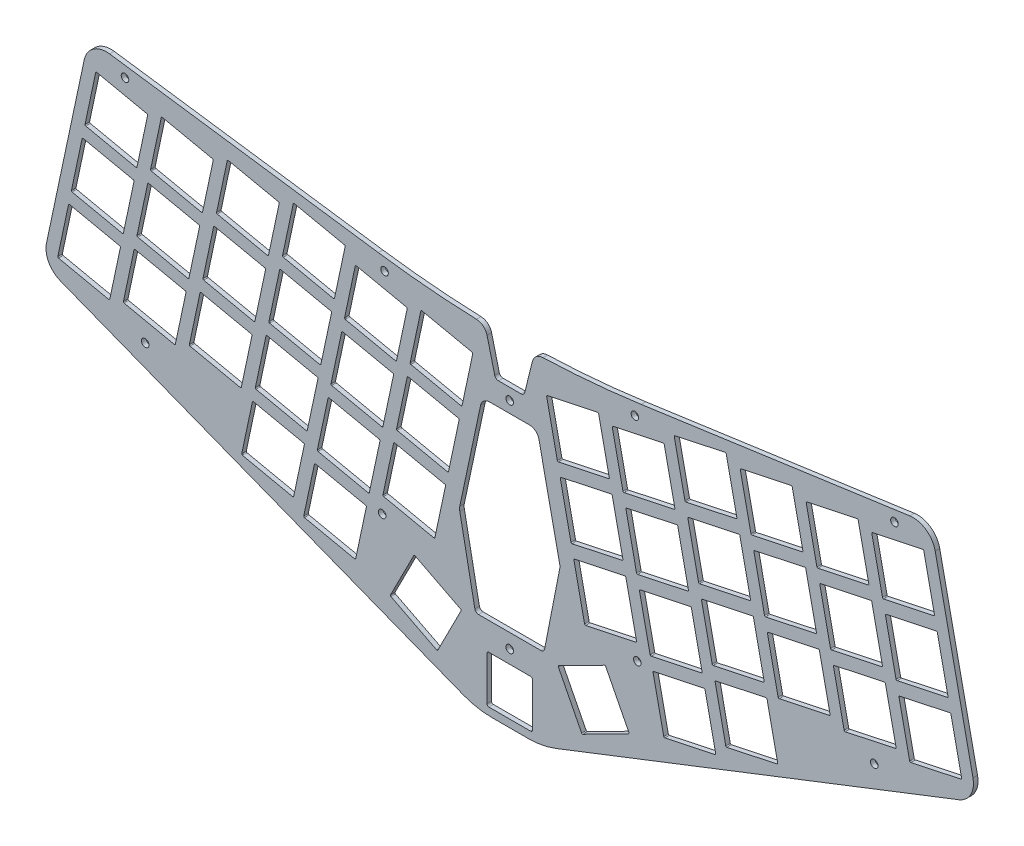
SolidWorks part; units mm, degrees
ref_plane "Front Plane" through (0, 0, 0) normal (0, 0, 1) x (1, 0, 0)
ref_plane "Top Plane" through (0, 0, 0) normal (0, 1, 0) x (1, 0, 0)
ref_plane "Right Plane" through (0, 0, 0) normal (1, 0, 0) x (0, 0, -1)
sketch "Model" plane through (0, 0, 0) normal (0, 0, 1) x (1, 0, 0)
  line L0 (118.9761, -36.3417) -> (119.3386, -36.3417)
  line L1 (109.9761, -36.3417) -> (109.6135, -36.3417)
  line L2 (130.2178, -33.5671) -> (126.6009, -34.9766)
  line L3 (98.7344, -33.5671) -> (102.3512, -34.9766)
  line L4 (114.4761, -36.3417) -> (109.9761, -36.3417)
  line L5 (114.4761, -36.3417) -> (118.9761, -36.3417)
  line L6 (118.4251, 42.1791) -> (120.4508, 50.3035)
  line L7 (110.527, 42.1791) -> (108.5014, 50.3035)
  line L8 (130.2178, -33.5671) -> (232.9153, 6.4558)
  line L9 (236.6055, 13.2938) -> (226.6558, 60.1035)
  line L10 (219.9519, 64.7976) -> (149.1302, 54.8443)
  line L11 (79.822, 54.8443) -> (9.0003, 64.7976)
  line L12 (2.2964, 60.1035) -> (-7.6533, 13.2938)
  line L13 (-3.9631, 6.4558) -> (98.7344, -33.5671)
  line L14 (111.4973, 41.421) -> (117.4548, 41.421)
  line L15 (119.9761, -34.3417) -> (108.9761, -34.3417)
  line L16 (120.4761, -22.3417) -> (120.4761, -33.8417)
  line L17 (108.9761, -21.8417) -> (119.9761, -21.8417)
  line L18 (108.4761, -33.8417) -> (108.4761, -22.3417)
  line L19 (123.6714, -13.7578) -> (127.6435, 6.5155)
  line L20 (105.2808, -13.7578) -> (101.3087, 6.5155)
  line L21 (106.2621, -14.5655) -> (122.69, -14.5655)
  line L22 (109.4761, 35.421) -> (109.2316, 35.421)
  line L23 (119.4761, 35.421) -> (119.7205, 35.421)
  line L24 (109.4761, 35.421) -> (119.4761, 35.421)
  line L25 (127.6339, 7.716) -> (122.1659, 33.4408)
  line L26 (101.3183, 7.716) -> (106.7863, 33.4408)
  line L27 (230.5128, 25.1235) -> (217.3078, 22.3167)
  line L28 (217.1153, 22.0202) -> (219.9221, 8.8152)
  line L29 (220.2186, 8.6226) -> (233.4236, 11.4294)
  line L30 (233.6161, 11.7259) -> (230.8093, 24.9309)
  line L31 (226.9263, 41.9965) -> (213.7213, 39.1897)
  line L32 (213.5288, 38.8932) -> (216.3356, 25.6882)
  line L33 (216.6321, 25.4957) -> (229.8371, 28.3025)
  line L34 (230.0297, 28.599) -> (227.2228, 41.804)
  line L35 (223.3399, 58.8696) -> (210.1349, 56.0628)
  line L36 (209.9423, 55.7663) -> (212.7491, 42.5613)
  line L37 (213.0456, 42.3687) -> (226.2506, 45.1755)
  line L38 (226.4432, 45.472) -> (223.6364, 58.677)
  line L39 (213.2239, 23.4933) -> (200.0189, 20.6865)
  line L40 (199.8264, 20.39) -> (202.6332, 7.185)
  line L41 (202.9297, 6.9924) -> (216.1347, 9.7992)
  line L42 (216.3273, 10.0958) -> (213.5205, 23.3007)
  line L43 (209.6375, 40.3663) -> (196.4325, 37.5595)
  line L44 (196.2399, 37.263) -> (199.0467, 24.058)
  line L45 (199.3432, 23.8655) -> (212.5482, 26.6723)
  line L46 (212.7408, 26.9688) -> (209.934, 40.1738)
  line L47 (206.051, 57.2394) -> (192.846, 54.4326)
  line L48 (192.6534, 54.1361) -> (195.4602, 40.9311)
  line L49 (195.7568, 40.7385) -> (208.9618, 43.5453)
  line L50 (209.1543, 43.8418) -> (206.3475, 57.0468)
  line L51 (195.8311, 22.3522) -> (182.6261, 19.5454)
  line L52 (182.4336, 19.2489) -> (185.2404, 6.0439)
  line L53 (185.5369, 5.8513) -> (198.7419, 8.6581)
  line L54 (198.9344, 8.9546) -> (196.1276, 22.1596)
  line L55 (192.2446, 39.2252) -> (179.0396, 36.4184)
  line L56 (178.8471, 36.1219) -> (181.6539, 22.9169)
  line L57 (181.9504, 22.7244) -> (195.1554, 25.5312)
  line L58 (195.348, 25.8277) -> (192.5412, 39.0327)
  line L59 (188.6582, 56.0983) -> (175.4532, 53.2915)
  line L60 (175.2606, 52.995) -> (178.0674, 39.79)
  line L61 (178.3639, 39.5974) -> (191.5689, 42.4042)
  line L62 (191.7615, 42.7007) -> (188.9547, 55.9057)
  line L63 (182.0248, 4.338) -> (168.8198, 1.5312)
  line L64 (168.6272, 1.2347) -> (171.434, -11.9703)
  line L65 (171.7305, -12.1628) -> (184.9355, -9.356)
  line L66 (185.1281, -9.0595) -> (182.3213, 4.1455)
  line L67 (178.4383, 21.2111) -> (165.2333, 18.4043)
  line L68 (165.0407, 18.1078) -> (167.8475, 4.9028)
  line L69 (168.1441, 4.7102) -> (181.3491, 7.517)
  line L70 (181.5416, 7.8135) -> (178.7348, 21.0185)
  line L71 (174.8518, 38.0841) -> (161.6468, 35.2773)
  line L72 (161.4543, 34.9808) -> (164.2611, 21.7758)
  line L73 (164.5576, 21.5833) -> (177.7626, 24.3901)
  line L74 (177.9551, 24.6866) -> (175.1483, 37.8916)
  line L75 (171.2653, 54.9572) -> (158.0603, 52.1504)
  line L76 (157.8678, 51.8539) -> (160.6746, 38.6489)
  line L77 (160.9711, 38.4563) -> (174.1761, 41.2631)
  line L78 (174.3687, 41.5596) -> (171.5619, 54.7646)
  line L79 (165.6715, -1.6938) -> (152.4665, -4.5006)
  line L80 (152.2739, -4.7971) -> (155.0808, -18.0021)
  line L81 (155.3773, -18.1947) -> (168.5823, -15.3879)
  line L82 (168.7748, -15.0914) -> (165.968, -1.8864)
  line L83 (162.085, 15.1792) -> (148.88, 12.3724)
  line L84 (148.6875, 12.0759) -> (151.4943, -1.1291)
  line L85 (151.7908, -1.3216) -> (164.9958, 1.4852)
  line L86 (165.1883, 1.7817) -> (162.3815, 14.9867)
  line L87 (158.4985, 32.0523) -> (145.2936, 29.2455)
  line L88 (145.101, 28.949) -> (147.9078, 15.744)
  line L89 (148.2043, 15.5514) -> (161.4093, 18.3582)
  line L90 (161.6019, 18.6547) -> (158.7951, 31.8597)
  line L91 (154.9121, 48.9253) -> (141.7071, 46.1185)
  line L92 (141.5145, 45.822) -> (144.3213, 32.617)
  line L93 (144.6178, 32.4245) -> (157.8228, 35.2313)
  line L94 (158.0154, 35.5278) -> (155.2086, 48.7328)
  line L95 (137.6232, 47.2952) -> (124.4182, 44.4883)
  line L96 (124.2256, 44.1918) -> (127.0325, 30.9868)
  line L97 (127.329, 30.7943) -> (140.534, 33.6011)
  line L98 (140.7265, 33.8976) -> (137.9197, 47.1026)
  line L99 (141.2097, 30.4221) -> (128.0047, 27.6153)
  line L100 (127.8121, 27.3188) -> (130.6189, 14.1138)
  line L101 (130.9154, 13.9212) -> (144.1204, 16.728)
  line L102 (144.313, 17.0246) -> (141.5062, 30.2295)
  line L103 (144.7962, 13.5491) -> (131.5912, 10.7423)
  line L104 (131.3986, 10.4457) -> (134.2054, -2.7593)
  line L105 (134.5019, -2.9518) -> (147.7069, -0.145)
  line L106 (147.8995, 0.1515) -> (145.0927, 13.3565)
  line L107 (139.4422, -9.5606) -> (127.4136, -15.6895)
  line L108 (127.3043, -16.0257) -> (133.4332, -28.0543)
  line L109 (133.7695, -28.1635) -> (145.7981, -22.0347)
  line L110 (145.9073, -21.6984) -> (139.7784, -9.6698)
  line L111 (101.5386, -15.6895) -> (89.51, -9.5606)
  line L112 (89.1737, -9.6698) -> (83.0449, -21.6984)
  line L113 (83.1541, -22.0347) -> (95.1827, -28.1635)
  line L114 (95.519, -28.0543) -> (101.6478, -16.0257)
  line L115 (97.361, 10.7423) -> (84.156, 13.5491)
  line L116 (83.8595, 13.3565) -> (81.0527, 0.1515)
  line L117 (81.2453, -0.145) -> (94.4502, -2.9518)
  line L118 (94.7468, -2.7593) -> (97.5536, 10.4457)
  line L119 (100.9475, 27.6153) -> (87.7425, 30.4221)
  line L120 (87.446, 30.2295) -> (84.6392, 17.0246)
  line L121 (84.8317, 16.728) -> (98.0367, 13.9212)
  line L122 (98.3332, 14.1138) -> (101.14, 27.3188)
  line L123 (104.534, 44.4883) -> (91.329, 47.2952)
  line L124 (91.0325, 47.1026) -> (88.2256, 33.8976)
  line L125 (88.4182, 33.6011) -> (101.6232, 30.7943)
  line L126 (101.9197, 30.9868) -> (104.7265, 44.1918)
  line L127 (76.4857, -4.5006) -> (63.2807, -1.6938)
  line L128 (62.9842, -1.8864) -> (60.1773, -15.0914)
  line L129 (60.3699, -15.3879) -> (73.5749, -18.1947)
  line L130 (73.8714, -18.0021) -> (76.6782, -4.7971)
  line L131 (80.0721, 12.3724) -> (66.8671, 15.1792)
  line L132 (66.5706, 14.9867) -> (63.7638, 1.7817)
  line L133 (63.9564, 1.4852) -> (77.1614, -1.3216)
  line L134 (77.4579, -1.1291) -> (80.2647, 12.0759)
  line L135 (83.6586, 29.2455) -> (70.4536, 32.0523)
  line L136 (70.1571, 31.8597) -> (67.3503, 18.6547)
  line L137 (67.5429, 18.3582) -> (80.7479, 15.5514)
  line L138 (81.0444, 15.744) -> (83.8512, 28.949)
  line L139 (87.2451, 46.1185) -> (74.0401, 48.9253)
  line L140 (73.7436, 48.7328) -> (70.9368, 35.5278)
  line L141 (71.1293, 35.2313) -> (84.3343, 32.4245)
  line L142 (84.6308, 32.617) -> (87.4377, 45.822)
  line L143 (60.1324, 1.5312) -> (46.9274, 4.338)
  line L144 (46.6309, 4.1455) -> (43.8241, -9.0595)
  line L145 (44.0166, -9.356) -> (57.2216, -12.1628)
  line L146 (57.5181, -11.9703) -> (60.325, 1.2347)
  line L147 (63.7189, 18.4043) -> (50.5139, 21.2111)
  line L148 (50.2174, 21.0185) -> (47.4106, 7.8135)
  line L149 (47.6031, 7.517) -> (60.8081, 4.7102)
  line L150 (61.1046, 4.9028) -> (63.9114, 18.1078)
  line L151 (67.3054, 35.2773) -> (54.1004, 38.0841)
  line L152 (53.8038, 37.8916) -> (50.997, 24.6866)
  line L153 (51.1896, 24.3901) -> (64.3946, 21.5833)
  line L154 (64.6911, 21.7758) -> (67.4979, 34.9808)
  line L155 (70.8918, 52.1504) -> (57.6868, 54.9572)
  line L156 (57.3903, 54.7646) -> (54.5835, 41.5596)
  line L157 (54.7761, 41.2631) -> (67.9811, 38.4563)
  line L158 (68.2776, 38.6489) -> (71.0844, 51.8539)
  line L159 (46.5186, 19.2489) -> (45.1152, 12.6464)
  line L160 (33.1211, 22.3522) -> (46.326, 19.5454)
  line L161 (30.0177, 8.9546) -> (32.8245, 22.1596)
  line L162 (43.4153, 5.8513) -> (30.2103, 8.6581)
  line L163 (45.1152, 12.6464) -> (43.7118, 6.0439)
  line L164 (50.1051, 36.1219) -> (48.7017, 29.5194)
  line L165 (36.7075, 39.2252) -> (49.9125, 36.4184)
  line L166 (33.6042, 25.8277) -> (36.411, 39.0327)
  line L167 (47.0018, 22.7244) -> (33.7968, 25.5312)
  line L168 (48.7017, 29.5194) -> (47.2983, 22.9169)
  line L169 (53.6916, 52.995) -> (52.2882, 46.3925)
  line L170 (40.294, 56.0983) -> (53.499, 53.2915)
  line L171 (37.1907, 42.7007) -> (39.9975, 55.9057)
  line L172 (50.5882, 39.5974) -> (37.3832, 42.4042)
  line L173 (52.2882, 46.3925) -> (50.8848, 39.79)
  line L174 (29.1258, 20.39) -> (27.7224, 13.7875)
  line L175 (15.7282, 23.4933) -> (28.9332, 20.6865)
  line L176 (12.6249, 10.0958) -> (15.4317, 23.3007)
  line L177 (26.0225, 6.9924) -> (12.8175, 9.7992)
  line L178 (27.7224, 13.7875) -> (26.319, 7.185)
  line L179 (32.7123, 37.263) -> (31.3089, 30.6605)
  line L180 (19.3147, 40.3663) -> (32.5197, 37.5595)
  line L181 (16.2114, 26.9688) -> (19.0182, 40.1738)
  line L182 (29.6089, 23.8655) -> (16.4039, 26.6723)
  line L183 (31.3089, 30.6605) -> (29.9055, 24.058)
  line L184 (19.7979, 43.8418) -> (21.2013, 50.4443)
  line L185 (33.1954, 40.7385) -> (19.9904, 43.5453)
  line L186 (36.2987, 54.1361) -> (33.4919, 40.9311)
  line L187 (22.9012, 57.2394) -> (36.1062, 54.4326)
  line L188 (21.2013, 50.4443) -> (22.6047, 57.0468)
  line L189 (-4.664, 11.7259) -> (-3.2606, 18.3284)
  line L190 (8.7336, 8.6226) -> (-4.4714, 11.4294)
  line L191 (11.8369, 22.0202) -> (9.0301, 8.8152)
  line L192 (-1.5606, 25.1235) -> (11.6444, 22.3167)
  line L193 (-3.2606, 18.3284) -> (-1.8572, 24.9309)
  line L194 (15.2308, 39.1897) -> (8.6283, 40.5931)
  line L195 (12.6166, 25.6882) -> (15.4234, 38.8932)
  line L196 (-0.8849, 28.3025) -> (12.3201, 25.4957)
  line L197 (1.7293, 41.804) -> (-1.0775, 28.599)
  line L198 (8.6283, 40.5931) -> (2.0258, 41.9965)
  line L199 (2.509, 45.472) -> (3.9124, 52.0745)
  line L200 (15.9065, 42.3687) -> (2.7016, 45.1755)
  line L201 (19.0099, 55.7663) -> (16.2031, 42.5613)
  line L202 (5.6123, 58.8696) -> (18.8173, 56.0628)
  line L203 (3.9124, 52.0745) -> (5.3158, 58.677)
  line L206 (114.4761, -19.3417) -> (114.4761, -17.3417) construction
  line L207 (115.4761, -18.3417) -> (113.4761, -18.3417) construction
  circle A0 centre (215.9057, 61.3788) radius 1
  circle A1 centre (13.0465, 61.3788) radius 1
  circle A2 centre (148.1114, -4.3098) radius 1
  circle A3 centre (80.8407, -4.3098) radius 1
  circle A4 centre (210.5718, 3.5051) radius 1
  circle A5 centre (147.4779, 51.4345) radius 1
  circle A6 centre (81.4742, 51.4345) radius 1
  circle A7 centre (18.3804, 3.5051) radius 1
  circle A8 centre (114.4761, -18.3417) radius 1
  circle A9 centre (114.4761, 38.421) radius 1
  arc A10 (108.4761, -33.8417) -> (108.9761, -34.3417) centre (108.9761, -33.8417) ccw
  arc A11 (119.9761, -34.3417) -> (120.4761, -33.8417) centre (119.9761, -33.8417) ccw
  arc A12 (120.4761, -22.3417) -> (119.9761, -21.8417) centre (119.9761, -22.3417) ccw
  arc A13 (108.9761, -21.8417) -> (108.4761, -22.3417) centre (108.9761, -22.3417) ccw
  arc A14 (122.69, -14.5655) -> (123.6714, -13.7578) centre (122.69, -13.5655) ccw
  arc A15 (105.2808, -13.7578) -> (106.2621, -14.5655) centre (106.2621, -13.5655) ccw
  arc A16 (127.6435, 6.5155) -> (127.6339, 7.716) centre (124.6994, 7.0923) ccw
  arc A17 (101.3183, 7.716) -> (101.3087, 6.5155) centre (104.2527, 7.0923) ccw
  arc A18 (122.1659, 33.4408) -> (119.7205, 35.421) centre (119.7205, 32.921) ccw
  arc A19 (109.2316, 35.421) -> (106.7863, 33.4408) centre (109.2316, 32.921) ccw
  arc A20 (46.5186, 19.2489) -> (46.326, 19.5454) centre (46.2741, 19.3008) ccw
  arc A21 (30.0177, 8.9546) -> (30.2103, 8.6581) centre (30.2623, 8.9027) ccw
  arc A22 (33.1211, 22.3522) -> (32.8245, 22.1596) centre (33.0691, 22.1077) ccw
  arc A23 (43.4153, 5.8513) -> (43.7118, 6.0439) centre (43.4673, 6.0959) ccw
  arc A24 (50.1051, 36.1219) -> (49.9125, 36.4184) centre (49.8605, 36.1739) ccw
  arc A25 (36.7075, 39.2252) -> (36.411, 39.0327) centre (36.6556, 38.9807) ccw
  arc A26 (33.6042, 25.8277) -> (33.7968, 25.5312) centre (33.8487, 25.7757) ccw
  arc A27 (47.0018, 22.7244) -> (47.2983, 22.9169) centre (47.0537, 22.9689) ccw
  arc A28 (53.6916, 52.995) -> (53.499, 53.2915) centre (53.447, 53.0469) ccw
  arc A29 (40.294, 56.0983) -> (39.9975, 55.9057) centre (40.242, 55.8537) ccw
  arc A30 (37.1907, 42.7007) -> (37.3832, 42.4042) centre (37.4352, 42.6488) ccw
  arc A31 (50.5882, 39.5974) -> (50.8848, 39.79) centre (50.6402, 39.8419) ccw
  arc A32 (29.1258, 20.39) -> (28.9332, 20.6865) centre (28.8812, 20.442) ccw
  arc A33 (15.7282, 23.4933) -> (15.4317, 23.3007) centre (15.6763, 23.2488) ccw
  arc A34 (12.6249, 10.0958) -> (12.8175, 9.7992) centre (12.8694, 10.0438) ccw
  arc A35 (26.0225, 6.9924) -> (26.319, 7.185) centre (26.0744, 7.237) ccw
  arc A36 (19.3147, 40.3663) -> (19.0182, 40.1738) centre (19.2627, 40.1218) ccw
  arc A37 (32.7123, 37.263) -> (32.5197, 37.5595) centre (32.4677, 37.315) ccw
  arc A38 (16.2114, 26.9688) -> (16.4039, 26.6723) centre (16.4559, 26.9168) ccw
  arc A39 (29.6089, 23.8655) -> (29.9055, 24.058) centre (29.6609, 24.11) ccw
  arc A40 (19.7979, 43.8418) -> (19.9904, 43.5453) centre (20.0424, 43.7899) ccw
  arc A41 (36.2987, 54.1361) -> (36.1062, 54.4326) centre (36.0542, 54.188) ccw
  arc A42 (33.1954, 40.7385) -> (33.4919, 40.9311) centre (33.2474, 40.9831) ccw
  arc A43 (22.9012, 57.2394) -> (22.6047, 57.0468) centre (22.8492, 56.9949) ccw
  arc A44 (-4.664, 11.7259) -> (-4.4714, 11.4294) centre (-4.4194, 11.674) ccw
  arc A45 (11.8369, 22.0202) -> (11.6444, 22.3167) centre (11.5924, 22.0721) ccw
  arc A46 (8.7336, 8.6226) -> (9.0301, 8.8152) centre (8.7856, 8.8671) ccw
  arc A47 (-1.5606, 25.1235) -> (-1.8572, 24.9309) centre (-1.6126, 24.8789) ccw
  arc A48 (15.4234, 38.8932) -> (15.2308, 39.1897) centre (15.1789, 38.9452) ccw
  arc A49 (12.3201, 25.4957) -> (12.6166, 25.6882) centre (12.372, 25.7402) ccw
  arc A50 (-1.0775, 28.599) -> (-0.8849, 28.3025) centre (-0.8329, 28.547) ccw
  arc A51 (2.0258, 41.9965) -> (1.7293, 41.804) centre (1.9739, 41.752) ccw
  arc A52 (2.509, 45.472) -> (2.7016, 45.1755) centre (2.7535, 45.42) ccw
  arc A53 (19.0099, 55.7663) -> (18.8173, 56.0628) centre (18.7653, 55.8182) ccw
  arc A54 (15.9065, 42.3687) -> (16.2031, 42.5613) centre (15.9585, 42.6132) ccw
  arc A55 (5.6123, 58.8696) -> (5.3158, 58.677) centre (5.5603, 58.625) ccw
  arc A56 (102.3512, -34.9766) -> (109.6135, -36.3417) centre (109.6135, -16.3417) ccw
  arc A57 (119.3386, -36.3417) -> (126.6009, -34.9766) centre (119.3386, -16.3417) ccw
  arc A58 (108.5014, 50.3035) -> (105.6963, 52.5758) centre (105.5905, 49.5777) ccw
  arc A59 (123.2559, 52.5758) -> (120.4508, 50.3035) centre (123.3617, 49.5777) ccw
  arc A60 (117.4548, 41.421) -> (118.4251, 42.1791) centre (117.4548, 42.421) ccw
  arc A61 (110.527, 42.1791) -> (111.4973, 41.421) centre (111.4973, 42.421) ccw
  arc A62 (232.9153, 6.4558) -> (236.6055, 13.2938) centre (230.7366, 12.0463) ccw
  arc A63 (226.6558, 60.1035) -> (219.9519, 64.7976) centre (220.7869, 58.856) ccw
  arc A64 (123.2559, 52.5758) -> (149.1302, 54.8443) centre (114.4761, 301.421) ccw
  arc A65 (79.822, 54.8443) -> (105.6963, 52.5758) centre (114.4761, 301.421) ccw
  arc A66 (9.0003, 64.7976) -> (2.2964, 60.1035) centre (8.1653, 58.856) ccw
  arc A67 (-7.6533, 13.2938) -> (-3.9631, 6.4558) centre (-1.7844, 12.0463) ccw
  arc A68 (217.3078, 22.3167) -> (217.1153, 22.0202) centre (217.3598, 22.0721) ccw
  arc A69 (219.9221, 8.8152) -> (220.2186, 8.6226) centre (220.1666, 8.8671) ccw
  arc A70 (233.4236, 11.4294) -> (233.6161, 11.7259) centre (233.3716, 11.674) ccw
  arc A71 (230.8093, 24.9309) -> (230.5128, 25.1235) centre (230.5648, 24.8789) ccw
  arc A72 (213.7213, 39.1897) -> (213.5288, 38.8932) centre (213.7733, 38.9452) ccw
  arc A73 (216.3356, 25.6882) -> (216.6321, 25.4957) centre (216.5801, 25.7402) ccw
  arc A74 (229.8371, 28.3025) -> (230.0297, 28.599) centre (229.7851, 28.547) ccw
  arc A75 (227.2228, 41.804) -> (226.9263, 41.9965) centre (226.9783, 41.752) ccw
  arc A76 (210.1349, 56.0628) -> (209.9423, 55.7663) centre (210.1868, 55.8182) ccw
  arc A77 (212.7491, 42.5613) -> (213.0456, 42.3687) centre (212.9937, 42.6132) ccw
  arc A78 (226.2506, 45.1755) -> (226.4432, 45.472) centre (226.1986, 45.42) ccw
  arc A79 (223.6364, 58.677) -> (223.3399, 58.8696) centre (223.3918, 58.625) ccw
  arc A80 (200.0189, 20.6865) -> (199.8264, 20.39) centre (200.0709, 20.442) ccw
  arc A81 (202.6332, 7.185) -> (202.9297, 6.9924) centre (202.8777, 7.237) ccw
  arc A82 (216.1347, 9.7992) -> (216.3273, 10.0958) centre (216.0827, 10.0438) ccw
  arc A83 (213.5205, 23.3007) -> (213.2239, 23.4933) centre (213.2759, 23.2488) ccw
  arc A84 (196.4325, 37.5595) -> (196.2399, 37.263) centre (196.4845, 37.315) ccw
  arc A85 (199.0467, 24.058) -> (199.3432, 23.8655) centre (199.2913, 24.11) ccw
  arc A86 (212.5482, 26.6723) -> (212.7408, 26.9688) centre (212.4963, 26.9168) ccw
  arc A87 (209.934, 40.1738) -> (209.6375, 40.3663) centre (209.6894, 40.1218) ccw
  arc A88 (192.846, 54.4326) -> (192.6534, 54.1361) centre (192.898, 54.188) ccw
  arc A89 (195.4602, 40.9311) -> (195.7568, 40.7385) centre (195.7048, 40.9831) ccw
  arc A90 (208.9618, 43.5453) -> (209.1543, 43.8418) centre (208.9098, 43.7899) ccw
  arc A91 (206.3475, 57.0468) -> (206.051, 57.2394) centre (206.103, 56.9949) ccw
  arc A92 (182.6261, 19.5454) -> (182.4336, 19.2489) centre (182.6781, 19.3008) ccw
  arc A93 (185.2404, 6.0439) -> (185.5369, 5.8513) centre (185.4849, 6.0959) ccw
  arc A94 (198.7419, 8.6581) -> (198.9344, 8.9546) centre (198.6899, 8.9027) ccw
  arc A95 (196.1276, 22.1596) -> (195.8311, 22.3522) centre (195.8831, 22.1077) ccw
  arc A96 (179.0396, 36.4184) -> (178.8471, 36.1219) centre (179.0916, 36.1739) ccw
  arc A97 (181.6539, 22.9169) -> (181.9504, 22.7244) centre (181.8984, 22.9689) ccw
  arc A98 (195.1554, 25.5312) -> (195.348, 25.8277) centre (195.1034, 25.7757) ccw
  arc A99 (192.5412, 39.0327) -> (192.2446, 39.2252) centre (192.2966, 38.9807) ccw
  arc A100 (175.4532, 53.2915) -> (175.2606, 52.995) centre (175.5051, 53.0469) ccw
  arc A101 (178.0674, 39.79) -> (178.3639, 39.5974) centre (178.312, 39.8419) ccw
  arc A102 (191.5689, 42.4042) -> (191.7615, 42.7007) centre (191.5169, 42.6488) ccw
  arc A103 (188.9547, 55.9057) -> (188.6582, 56.0983) centre (188.7101, 55.8537) ccw
  arc A104 (168.8198, 1.5312) -> (168.6272, 1.2347) centre (168.8718, 1.2867) ccw
  arc A105 (171.434, -11.9703) -> (171.7305, -12.1628) centre (171.6786, -11.9183) ccw
  arc A106 (184.9355, -9.356) -> (185.1281, -9.0595) centre (184.8836, -9.1115) ccw
  arc A107 (182.3213, 4.1455) -> (182.0248, 4.338) centre (182.0767, 4.0935) ccw
  arc A108 (165.2333, 18.4043) -> (165.0407, 18.1078) centre (165.2853, 18.1597) ccw
  arc A109 (167.8475, 4.9028) -> (168.1441, 4.7102) centre (168.0921, 4.9547) ccw
  arc A110 (181.3491, 7.517) -> (181.5416, 7.8135) centre (181.2971, 7.7616) ccw
  arc A111 (178.7348, 21.0185) -> (178.4383, 21.2111) centre (178.4903, 20.9665) ccw
  arc A112 (161.6468, 35.2773) -> (161.4543, 34.9808) centre (161.6988, 35.0328) ccw
  arc A113 (164.2611, 21.7758) -> (164.5576, 21.5833) centre (164.5056, 21.8278) ccw
  arc A114 (177.7626, 24.3901) -> (177.9551, 24.6866) centre (177.7106, 24.6346) ccw
  arc A115 (175.1483, 37.8916) -> (174.8518, 38.0841) centre (174.9038, 37.8396) ccw
  arc A116 (158.0603, 52.1504) -> (157.8678, 51.8539) centre (158.1123, 51.9058) ccw
  arc A117 (160.6746, 38.6489) -> (160.9711, 38.4563) centre (160.9191, 38.7008) ccw
  arc A118 (174.1761, 41.2631) -> (174.3687, 41.5596) centre (174.1241, 41.5076) ccw
  arc A119 (171.5619, 54.7646) -> (171.2653, 54.9572) centre (171.3173, 54.7126) ccw
  arc A120 (152.4665, -4.5006) -> (152.2739, -4.7971) centre (152.5185, -4.7452) ccw
  arc A121 (155.0808, -18.0021) -> (155.3773, -18.1947) centre (155.3253, -17.9501) ccw
  arc A122 (168.5823, -15.3879) -> (168.7748, -15.0914) centre (168.5303, -15.1433) ccw
  arc A123 (165.968, -1.8864) -> (165.6715, -1.6938) centre (165.7235, -1.9383) ccw
  arc A124 (148.88, 12.3724) -> (148.6875, 12.0759) centre (148.932, 12.1279) ccw
  arc A125 (151.4943, -1.1291) -> (151.7908, -1.3216) centre (151.7388, -1.0771) ccw
  arc A126 (164.9958, 1.4852) -> (165.1883, 1.7817) centre (164.9438, 1.7297) ccw
  arc A127 (162.3815, 14.9867) -> (162.085, 15.1792) centre (162.137, 14.9347) ccw
  arc A128 (145.2936, 29.2455) -> (145.101, 28.949) centre (145.3455, 29.0009) ccw
  arc A129 (147.9078, 15.744) -> (148.2043, 15.5514) centre (148.1523, 15.7959) ccw
  arc A130 (161.4093, 18.3582) -> (161.6019, 18.6547) centre (161.3573, 18.6028) ccw
  arc A131 (158.7951, 31.8597) -> (158.4985, 32.0523) centre (158.5505, 31.8078) ccw
  arc A132 (141.7071, 46.1185) -> (141.5145, 45.822) centre (141.7591, 45.874) ccw
  arc A133 (144.3213, 32.617) -> (144.6178, 32.4245) centre (144.5659, 32.669) ccw
  arc A134 (157.8228, 35.2313) -> (158.0154, 35.5278) centre (157.7709, 35.4758) ccw
  arc A135 (155.2086, 48.7328) -> (154.9121, 48.9253) centre (154.964, 48.6808) ccw
  arc A136 (124.4182, 44.4883) -> (124.2256, 44.1918) centre (124.4702, 44.2438) ccw
  arc A137 (127.0325, 30.9868) -> (127.329, 30.7943) centre (127.277, 31.0388) ccw
  arc A138 (140.534, 33.6011) -> (140.7265, 33.8976) centre (140.482, 33.8456) ccw
  arc A139 (137.9197, 47.1026) -> (137.6232, 47.2952) centre (137.6752, 47.0506) ccw
  arc A140 (128.0047, 27.6153) -> (127.8121, 27.3188) centre (128.0567, 27.3708) ccw
  arc A141 (130.6189, 14.1138) -> (130.9154, 13.9212) centre (130.8635, 14.1658) ccw
  arc A142 (144.1204, 16.728) -> (144.313, 17.0246) centre (144.0685, 16.9726) ccw
  arc A143 (141.5062, 30.2295) -> (141.2097, 30.4221) centre (141.2617, 30.1776) ccw
  arc A144 (131.5912, 10.7423) -> (131.3986, 10.4457) centre (131.6431, 10.4977) ccw
  arc A145 (134.2054, -2.7593) -> (134.5019, -2.9518) centre (134.4499, -2.7073) ccw
  arc A146 (147.7069, -0.145) -> (147.8995, 0.1515) centre (147.6549, 0.0995) ccw
  arc A147 (145.0927, 13.3565) -> (144.7962, 13.5491) centre (144.8481, 13.3045) ccw
  arc A148 (127.4136, -15.6895) -> (127.3043, -16.0257) centre (127.5271, -15.9122) ccw
  arc A149 (133.4332, -28.0543) -> (133.7695, -28.1635) centre (133.656, -27.9408) ccw
  arc A150 (145.7981, -22.0347) -> (145.9073, -21.6984) centre (145.6846, -21.8119) ccw
  arc A151 (139.7784, -9.6698) -> (139.4422, -9.5606) centre (139.5557, -9.7833) ccw
  arc A152 (89.51, -9.5606) -> (89.1737, -9.6698) centre (89.3965, -9.7833) ccw
  arc A153 (83.0449, -21.6984) -> (83.1541, -22.0347) centre (83.2676, -21.8119) ccw
  arc A154 (95.1827, -28.1635) -> (95.519, -28.0543) centre (95.2962, -27.9408) ccw
  arc A155 (101.6478, -16.0257) -> (101.5386, -15.6895) centre (101.4251, -15.9122) ccw
  arc A156 (84.156, 13.5491) -> (83.8595, 13.3565) centre (84.104, 13.3045) ccw
  arc A157 (81.0527, 0.1515) -> (81.2453, -0.145) centre (81.2972, 0.0995) ccw
  arc A158 (94.4502, -2.9518) -> (94.7468, -2.7593) centre (94.5022, -2.7073) ccw
  arc A159 (97.5536, 10.4457) -> (97.361, 10.7423) centre (97.309, 10.4977) ccw
  arc A160 (87.7425, 30.4221) -> (87.446, 30.2295) centre (87.6905, 30.1776) ccw
  arc A161 (84.6392, 17.0246) -> (84.8317, 16.728) centre (84.8837, 16.9726) ccw
  arc A162 (98.0367, 13.9212) -> (98.3332, 14.1138) centre (98.0887, 14.1658) ccw
  arc A163 (101.14, 27.3188) -> (100.9475, 27.6153) centre (100.8955, 27.3708) ccw
  arc A164 (91.329, 47.2952) -> (91.0325, 47.1026) centre (91.277, 47.0506) ccw
  arc A165 (88.2256, 33.8976) -> (88.4182, 33.6011) centre (88.4702, 33.8456) ccw
  arc A166 (101.6232, 30.7943) -> (101.9197, 30.9868) centre (101.6752, 31.0388) ccw
  arc A167 (104.7265, 44.1918) -> (104.534, 44.4883) centre (104.482, 44.2438) ccw
  arc A168 (63.2807, -1.6938) -> (62.9842, -1.8864) centre (63.2287, -1.9383) ccw
  arc A169 (60.1773, -15.0914) -> (60.3699, -15.3879) centre (60.4219, -15.1433) ccw
  arc A170 (73.5749, -18.1947) -> (73.8714, -18.0021) centre (73.6269, -17.9501) ccw
  arc A171 (76.6782, -4.7971) -> (76.4857, -4.5006) centre (76.4337, -4.7452) ccw
  arc A172 (66.8671, 15.1792) -> (66.5706, 14.9867) centre (66.8152, 14.9347) ccw
  arc A173 (63.7638, 1.7817) -> (63.9564, 1.4852) centre (64.0084, 1.7297) ccw
  arc A174 (77.1614, -1.3216) -> (77.4579, -1.1291) centre (77.2134, -1.0771) ccw
  arc A175 (80.2647, 12.0759) -> (80.0721, 12.3724) centre (80.0202, 12.1279) ccw
  arc A176 (70.4536, 32.0523) -> (70.1571, 31.8597) centre (70.4016, 31.8078) ccw
  arc A177 (67.3503, 18.6547) -> (67.5429, 18.3582) centre (67.5948, 18.6028) ccw
  arc A178 (80.7479, 15.5514) -> (81.0444, 15.744) centre (80.7998, 15.7959) ccw
  arc A179 (83.8512, 28.949) -> (83.6586, 29.2455) centre (83.6066, 29.0009) ccw
  arc A180 (74.0401, 48.9253) -> (73.7436, 48.7328) centre (73.9881, 48.6808) ccw
  arc A181 (70.9368, 35.5278) -> (71.1293, 35.2313) centre (71.1813, 35.4758) ccw
  arc A182 (84.3343, 32.4245) -> (84.6308, 32.617) centre (84.3863, 32.669) ccw
  arc A183 (87.4377, 45.822) -> (87.2451, 46.1185) centre (87.1931, 45.874) ccw
  arc A184 (46.9274, 4.338) -> (46.6309, 4.1455) centre (46.8754, 4.0935) ccw
  arc A185 (43.8241, -9.0595) -> (44.0166, -9.356) centre (44.0686, -9.1115) ccw
  arc A186 (57.2216, -12.1628) -> (57.5181, -11.9703) centre (57.2736, -11.9183) ccw
  arc A187 (60.325, 1.2347) -> (60.1324, 1.5312) centre (60.0804, 1.2867) ccw
  arc A188 (50.5139, 21.2111) -> (50.2174, 21.0185) centre (50.4619, 20.9665) ccw
  arc A189 (47.4106, 7.8135) -> (47.6031, 7.517) centre (47.6551, 7.7616) ccw
  arc A190 (60.8081, 4.7102) -> (61.1046, 4.9028) centre (60.8601, 4.9547) ccw
  arc A191 (63.9114, 18.1078) -> (63.7189, 18.4043) centre (63.6669, 18.1597) ccw
  arc A192 (54.1004, 38.0841) -> (53.8038, 37.8916) centre (54.0484, 37.8396) ccw
  arc A193 (50.997, 24.6866) -> (51.1896, 24.3901) centre (51.2416, 24.6346) ccw
  arc A194 (64.3946, 21.5833) -> (64.6911, 21.7758) centre (64.4466, 21.8278) ccw
  arc A195 (67.4979, 34.9808) -> (67.3054, 35.2773) centre (67.2534, 35.0328) ccw
  arc A196 (57.6868, 54.9572) -> (57.3903, 54.7646) centre (57.6349, 54.7126) ccw
  arc A197 (54.5835, 41.5596) -> (54.7761, 41.2631) centre (54.828, 41.5076) ccw
  arc A198 (67.9811, 38.4563) -> (68.2776, 38.6489) centre (68.033, 38.7008) ccw
  arc A199 (71.0844, 51.8539) -> (70.8918, 52.1504) centre (70.8399, 51.9058) ccw
extrude "Boss-Extrude1" add sketch "Model" along normal blind 1.2
sketch "Sketch1" plane through (0, 0, 1.2) normal (0, 0, 1) x (1, 0, 0)
  line L0 (113.4761, 38.421) -> (115.4761, 38.421) construction
  line L1 (114.4761, 37.421) -> (114.4761, 39.421) construction
  line L2 (113.4761, -18.3417) -> (115.4761, -18.3417)
  line L3 (114.4761, -19.3417) -> (114.4761, -17.3417)
  circle A0 centre (114.4761, 38.421) radius 1 construction
  circle A1 centre (114.4761, -18.3417) radius 1 construction
